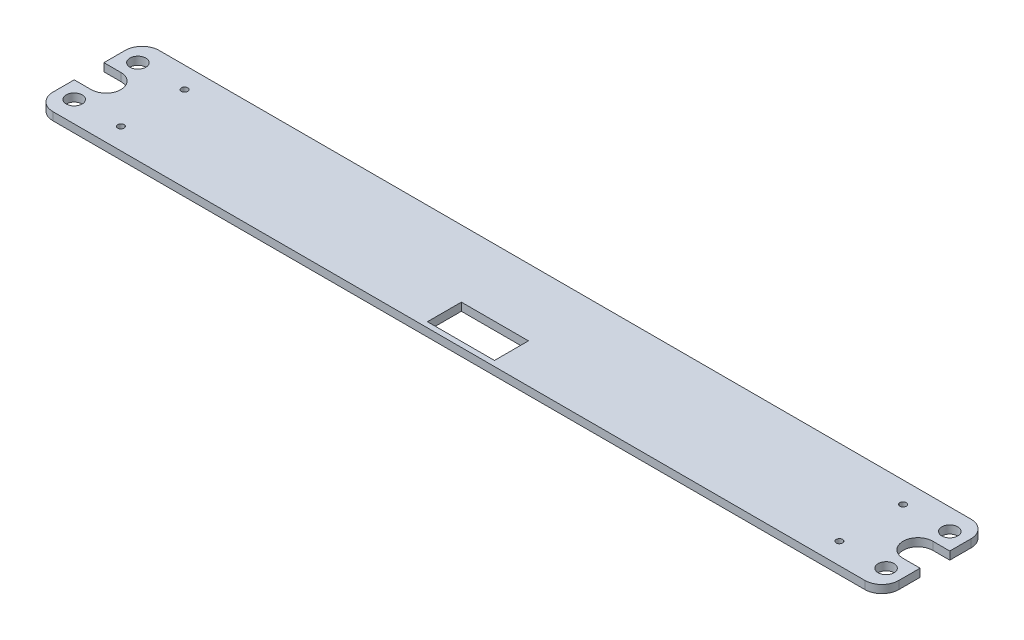
SolidWorks part; units mm, degrees
ref_plane "Front Plane" through (0, 0, 0) normal (0, 0, 1) x (1, 0, 0)
ref_plane "Top Plane" through (0, 0, 0) normal (0, 1, 0) x (1, 0, 0)
ref_plane "Right Plane" through (0, 0, 0) normal (1, 0, 0) x (0, 0, -1)
sketch "Sketch1" plane through (0, 0, 0) normal (0, 1, 0) x (1, 0, 0)
  line L0 (0, -31.75) -> (1.27, -31.75) construction
  line L1 (10.16, 0) -> (253.0475, 0)
  line L2 (0, -10.16) -> (0, -22.86)
  line L3 (10.16, -63.5) -> (253.0475, -63.5)
  line L5 (10.16, -40.64) -> (0, -40.64)
  line L6 (10.16, -22.86) -> (0, -22.86)
  line L7 (0, -40.64) -> (0, -53.34)
  line L8 (19.05, -31.75) -> (87.4324, -31.75) construction
  line L14 (253.0475, -63.5) -> (253.0475, 0)
  circle A0 centre (10.16, -50.8) radius 4.7625
  circle A1 centre (10.16, -12.7) radius 4.7625
  arc A2 (10.16, -40.64) -> (10.16, -22.86) centre (10.16, -31.75) ccw
  circle A3 centre (10.16, -12.7) radius 6.35 construction
  circle A4 centre (10.16, -50.8) radius 6.35 construction
  arc A5 (0, -53.34) -> (10.16, -63.5) centre (10.16, -53.34) ccw
  arc A6 (10.16, 0) -> (0, -10.16) centre (10.16, -10.16) ccw
  circle A7 centre (38.1, -50.8) radius 1.905
  circle A8 centre (38.1, -12.7) radius 1.905
  point P1 (0, -16.51)
  point P22 (0, -63.5)
  point P25 (0, 0)
  point P38 (50.8, -63.5)
  dimension "D3" = 9.525
  dimension "D4" = 9.525
  dimension "D5" = 17.78
  dimension "D10" = 31.75
  dimension "D11" = 12.7
  dimension "D12" = 12.7
  dimension "D13" = 10.16
  dimension "D14" = 3.81
  dimension "D15" = 3.81
  dimension "D1" = 63.5
  dimension "D2" = 50.8
  dimension "D6" = 19.05
  dimension "D7" = 19.05
  dimension "D8" = 10.16
  dimension "D9" = 10.16
  dimension "D16" = 12.7
  dimension "D17" = 12.7
  dimension "D18" = 253.0475
  dimension "D19" = 253.0475
  dimension "D20" = 38.1
extrude "Boss-Extrude1" add sketch "Sketch1" along normal blind 4.7625
mirror "Mirror1" about plane through (253.0475, 4.7625, 63.5) normal (-1, 0, 0) of "Boss-Extrude1"
sketch "Sketch2" plane through (0, 4.7625, 0) normal (0, 1, 0) x (1, 0, 0)
  line L0 (506.095, -40.64) -> (506.095, -53.34) construction
  line L1 (231.013, -60.325) -> (271.145, -60.325)
  line L2 (231.013, -60.325) -> (231.013, -40.005)
  line L3 (231.013, -40.005) -> (271.145, -40.005)
  line L4 (271.145, -60.325) -> (271.145, -40.005)
  line L5 (10.16, -63.5) -> (495.935, -63.5) construction
  dimension "D1" = 234.95
  dimension "D2" = 40.132
  dimension "D3" = 20.32
  dimension "D4" = 3.175
extrude "Cut-Extrude1" cut sketch "Sketch2" against normal through all
